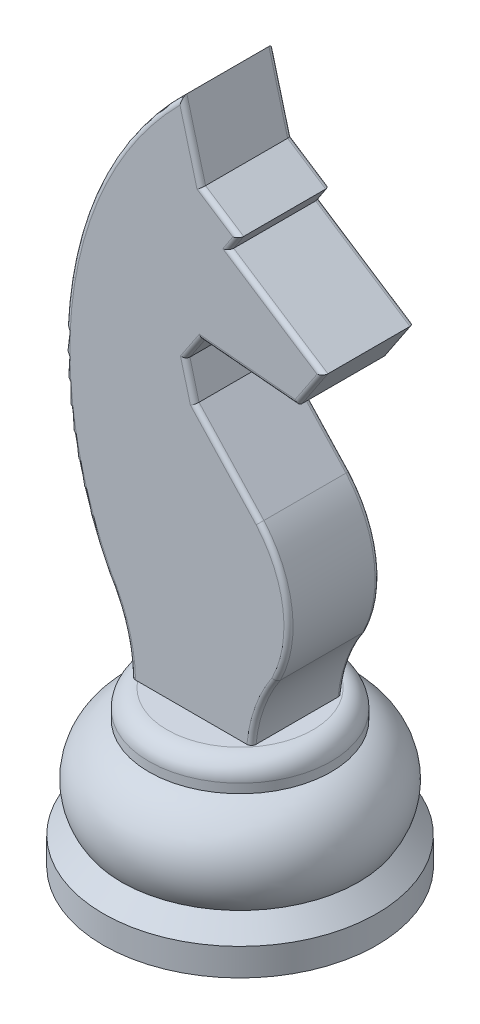
SolidWorks part; units mm, degrees
ref_plane "Ön Düzlem" through (0, 0, 0) normal (0, 0, 1) x (1, 0, 0)
ref_plane "Üst Düzlem" through (0, 0, 0) normal (0, 1, 0) x (1, 0, 0)
ref_plane "Sağ Düzlem" through (0, 0, 0) normal (1, 0, 0) x (0, 0, -1)
sketch "Çizim1" plane through (0, 0, 0) normal (0, 0, 1) x (1, 0, 0)
  line L0 (0, 83.9462) -> (0, -16.1787) construction
  line L1 (0, 0) -> (-15, 0)
  line L2 (-15, 0) -> (-15, 3)
  line L3 (-15, 3) -> (-13, 5)
  line L6 (-10, 13.97) -> (-10, 14.97)
  line L8 (-8, 16.97) -> (0, 16.97)
  line L9 (0, 16.97) -> (0, 0)
  arc A0 (-13, 5) -> (-10, 13.97) centre (-7.9981, 8.3138) cw
  arc A1 (-10, 14.97) -> (-8, 16.97) centre (-8, 14.97) cw
  dimension "D9" = 6
  dimension "D10" = 2
  dimension "D1" = 15
  dimension "D3" = 3
  dimension "D4" = 2
  dimension "D6" = 1
  dimension "D11" = 8
revolve "Döndür1" add sketch "Çizim1" angle 360 about L0
sketch "Çizim2" plane through (0, 0, 0) normal (0, 0, 1) x (1, 0, 0)
  line L0 (-1.33, 75) -> (0.7172, 67.29)
  line L1 (0.7172, 67.29) -> (4.8972, 64.56)
  line L2 (4.8972, 64.56) -> (3.8, 62.88)
  line L3 (3.8, 62.88) -> (14.14, 56.1268)
  line L4 (14.14, 56.1268) -> (11.3, 51.87)
  line L5 (11.3, 51.87) -> (0.78, 52.81)
  line L6 (0.78, 52.81) -> (-1, 50.142)
  line L7 (-1, 50.142) -> (0, 46.35)
  line L8 (0, 46.35) -> (7.12, 38.68)
  line L9 (8, 16.97) -> (-8, 16.97) construction
  line L10 (-6.9652, 16.97) -> (6.2548, 16.97)
  line L16 (10.31, 29.87) -> (13.391, 29.87)
  arc A0 (-6.9652, 16.97) -> (-9.6035, 25.6724) centre (-23.7617, 16.6289) ccw
  arc A1 (8.9378, 24.4194) -> (6.2548, 16.97) centre (22.2593, 15.4137) ccw
  arc A2 (-9.6035, 25.6724) -> (-1.33, 75) centre (27.8972, 44.7402) cw
  arc A3 (8.9378, 24.4194) -> (7.12, 38.68) centre (-2.5281, 30.204) ccw
  dimension "D17" = 16.08
  dimension "D18" = 42.07
  dimension "D20" = 16.8
  dimension "D1" = 1.33
  dimension "D2" = 4.18
  dimension "D3" = 14.14
  dimension "D4" = 3.8
  dimension "D5" = 75
  dimension "D6" = 47.59
  dimension "D7" = 45.91
  dimension "D8" = 50.32
  dimension "D9" = 34.9
  dimension "D10" = 35.84
  dimension "D11" = 12.3
  dimension "D12" = 1
  dimension "D13" = 0.78
  dimension "D14" = 7.12
  dimension "D15" = 21.71
  dimension "D16" = 29.38
  dimension "D21" = 13.22
  dimension "D23" = 12.9
  dimension "D24" = 10.31
extrude "Yükseklik-Ekstrüzyon1" add sketch "Çizim2" along normal blind 5 and the other way blind 5 contours A1 A3 L8 L7 L6 L5 L4 L3 L2 L1 L0 A2 A0 L10 region at (-2.1248, 42.9671, 0)
fillet "Radyus1" radius 0.5 26 edges at (3.56, 42.515, 5) (-0.5, 48.246, 5) (-0.11, 51.476, 5) (6.04, 52.34, 5) (12.72, 53.9984, 5) (-0.3064, 71.145, 5) (4.3486, 63.72, 5) (2.8072, 65.925, 5) (8.97, 59.5034, 5) (-13.5932, 51.6992, 5) (-7.6843, 21.5031, 5) (7.1306, 20.8624, 5) (10.2113, 31.8279, 5) (7.1306, 20.8624, -5) (3.56, 42.515, -5) (-0.5, 48.246, -5) (-0.11, 51.476, -5) (6.04, 52.34, -5) (12.72, 53.9984, -5) (4.3486, 63.72, -5) (8.97, 59.5034, -5) (2.8072, 65.925, -5) (-0.3064, 71.145, -5) (-13.5932, 51.6992, -5) (-7.6843, 21.5031, -5) (10.2113, 31.8279, -5)
